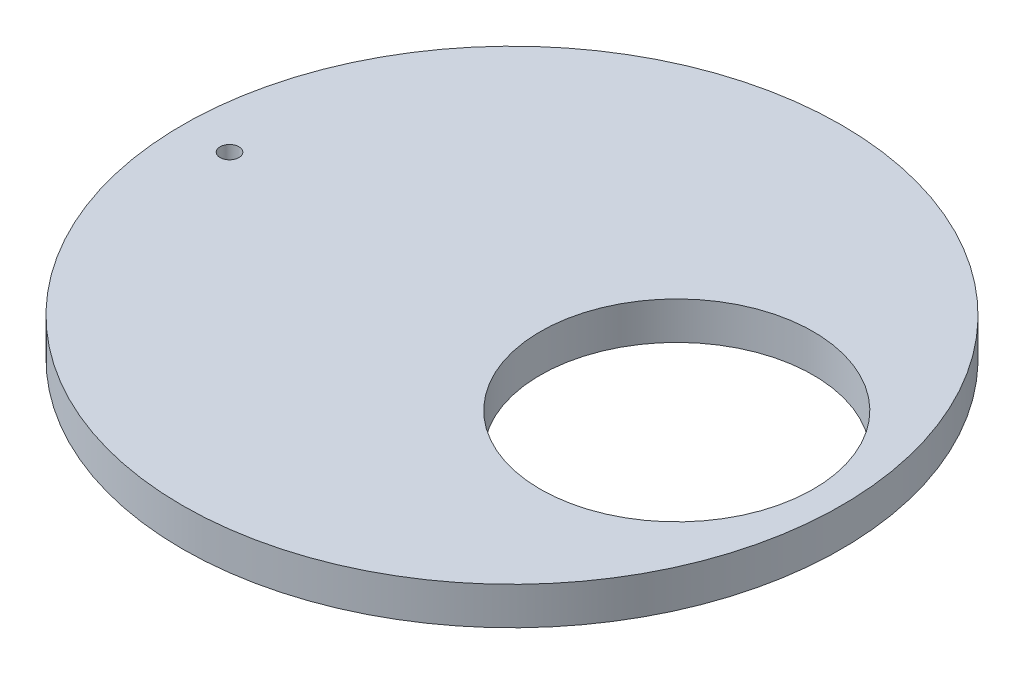
SolidWorks part; units mm, degrees
ref_plane "Front Plane" through (0, 0, 0) normal (0, 0, 1) x (1, 0, 0)
ref_plane "Top Plane" through (0, 0, 0) normal (0, 1, 0) x (1, 0, 0)
ref_plane "Right Plane" through (0, 0, 0) normal (1, 0, 0) x (0, 0, -1)
sketch "Sketch1" plane through (0, 0, 0) normal (0, 1, 0) x (1, 0, 0)
  circle A0 centre (0, 0) radius 70
  arc A1 (35, 29) -> (35, -29) centre (35, 0) ccw
  circle A2 centre (35, 0) radius 29
  point P4 (63.7103, 29.479)
  dimension "D1" = 140
  dimension "D2" = 58
  dimension "D3" = 35
extrude "Boss-Extrude1" add sketch "Sketch1" along normal blind 8 contours A0 A2 A1 region at (-7.2518, 0, 0)
sketch "Sketch2" plane through (0, 8, 0) normal (0, 1, 0) x (1, 0, 0)
  circle A0 centre (-60, -0.0015) radius 2
  dimension "D1" = 4
extrude "Cut-Extrude1" cut sketch "Sketch2" against normal up to next
sketch "Sketch3" plane through (0, 0, 0) normal (0, -1, 0) x (1, 0, 0)
  circle A0 centre (-60, 0.0015) radius 2.4
  dimension "D1" = 4.8
extrude "Cut-Extrude2" cut sketch "Sketch3" against normal blind 2
